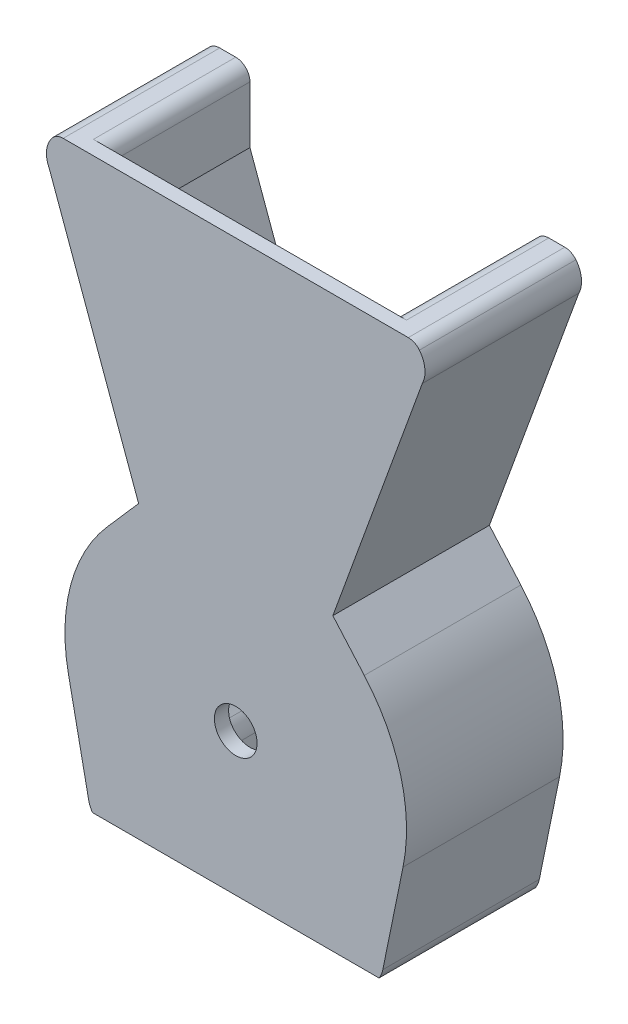
SolidWorks part; units mm, degrees
ref_plane "Front Plane" through (0, 0, 0) normal (0, 0, 1) x (1, 0, 0)
ref_plane "Top Plane" through (0, 0, 0) normal (0, 1, 0) x (1, 0, 0)
ref_plane "Right Plane" through (0, 0, 0) normal (1, 0, 0) x (0, 0, -1)
sketch "Boundaries" plane through (0, 0, 0) normal (0, 0, 1) x (1, 0, 0)
  line L1 (-80, 100) -> (80, 100) construction
  line L2 (-80, 100) -> (-80, -100) construction
  line L3 (-80, -100) -> (80, -100) construction
  line L4 (80, 100) -> (80, -100) construction
  point P0 (0, 0)
  point P7 (0, 100)
  point P8 (80, 0)
  dimension "D1" = 160
  dimension "D2" = 200
sketch "Sketch2" plane through (0, 0, 0) normal (0, 0, 1) x (1, 0, 0)
  line L0 (-80, -100) -> (80, -100) construction
  line L1 (-53.1957, 0) -> (53.1957, 0) construction
  line L4 (-50, 75) -> (50, 75) construction
  line L5 (-50, 75) -> (-22.7022, 0)
  line L6 (50, 75) -> (22.7022, 0)
  line L7 (-53.1957, 0) -> (-22.7022, 0) construction
  line L8 (-80, 100) -> (-50, 100)
  line L9 (-80, 100) -> (-80, -100)
  line L10 (-80, -100) -> (-35.3553, -100)
  line L11 (80, 100) -> (80, -100)
  line L12 (22.7022, 0) -> (53.1957, 0) construction
  line L13 (-50, 75) -> (-50, 100)
  line L14 (50, 75) -> (50, 100)
  line L15 (50, 100) -> (80, 100)
  line L16 (-37.6439, -17.092) -> (-22.7022, 0)
  line L17 (22.7022, 0) -> (37.6439, -17.092)
  line L20 (35.3553, -100) -> (80, -100)
  line L21 (-35.3553, -100) -> (35.3553, -100) construction
  line L22 (-35.3553, -14.6447) -> (35.3553, -85.3553) construction
  line L23 (-35.3553, -85.3553) -> (35.3553, -14.6447) construction
  line L24 (0, 0) -> (0, -50) construction
  line L26 (-35.3553, -100) -> (-35.3553, -85.3553)
  line L27 (35.3553, -100) -> (35.3553, -85.3553)
  arc A0 (-37.6439, -17.092) -> (-35.3553, -85.3553) centre (0, -50) ccw construction
  arc A1 (-37.6439, -17.092) -> (-35.3553, -85.3553) centre (0, -50) ccw
  arc A2 (35.3553, -85.3553) -> (37.6439, -17.092) centre (0, -50) ccw construction
  arc A3 (35.3553, -85.3553) -> (37.6439, -17.092) centre (0, -50) ccw
  circle A4 centre (0, -50) radius 50 construction
  point P12 (0, 0)
  point P13 (0, 75)
  point P26 (0, -100)
  point P31 (0, -50)
  point P34 (0, -50)
  dimension "D1" = 100
  dimension "D2" = 45
  dimension "D3" = 45
  dimension "D4" = 70
  dimension "D5" = 70
  dimension "D8" = 100
  dimension "D9" = 75
  dimension "D10" = 45.4045
extrude "Boss-Extrude1" add sketch "Sketch2" against normal blind 50
sketch "Sketch3" plane through (0, 0, 0) normal (0, 0, 1) x (1, 0, 0)
  line L0 (-29.9816, 20) -> (29.9816, 20)
  line L1 (-50, 75) -> (-22.7022, 0) construction
  line L2 (50, 75) -> (22.7022, 0) construction
  line L3 (29.9816, 20) -> (22.7022, 0)
  line L4 (22.7022, 0) -> (-22.7022, 0)
  line L5 (-22.7022, 0) -> (-29.9816, 20)
  dimension "D1" = 20
extrude "Boss-Extrude2" add sketch "Sketch3" against normal blind 10
chamfer "Chamfer1" distance 20 distance2 15 1 edges at (0, 20, -10) first distance on face at (0, 10, -10)
sketch "Sketch4" plane through (0, 0, 0) normal (0, 0, 1) x (1, 0, 0)
  line L1 (-80, 100) -> (80, 100)
  line L2 (-80, 100) -> (-80, -100)
  line L3 (-80, -100) -> (80, -100)
  line L4 (80, 100) -> (80, -100)
extrude "Boss-Extrude3" add sketch "Sketch4" along normal blind 5
fillet "Fillet1" radius 10 5 edges at (-35.3553, -85.3553, -25) (-22.7022, 0, -30) (22.7022, 0, -30) (0, 13.3333, 0) (35.3553, -85.3553, -25)
sketch "Sketch5" plane through (0, 0, 0) normal (0, 0, -1) x (-1, 0, 0)
  circle A0 centre (0, -50) radius 7.5
  dimension "D1" = 15
extrude "Cut-Extrude1" cut sketch "Sketch5" against normal up to surface (5 mm away) up to face at (0, 0, 5)
sketch "Sketch11" plane through (0, 0, -50) normal (0, 0, -1) x (-1, 0, 0)
  line L0 (80, -100) -> (-80, -100) construction
  line L1 (-35.3553, -100) -> (-35.3553, -85.3553) construction
  line L2 (-58.7842, -62.0174) -> (-51.673, -96.8026)
  line L3 (-80, -100) -> (-50.3387, -100)
  line L4 (0, -100) -> (0, 100) construction
  line L5 (34.1202, 2.1327) -> (45.1727, -10.5104)
  line L6 (60, 73.2367) -> (34.1202, 2.1327)
  line L7 (60, 73.2367) -> (65.537, 88.4494)
  line L8 (80, 100) -> (-80, 100) construction
  line L9 (-50, 75) -> (-50, 100) construction
  line L10 (-60, 73.2367) -> (-65.537, 88.4494)
  line L11 (-80, 100) -> (-80, -100) construction
  line L12 (-45.3553, -89.2797) -> (-45.3553, -100)
  line L13 (-34.1202, 2.1327) -> (-45.1727, -10.5104)
  line L14 (-60, 73.2367) -> (-34.1202, 2.1327)
  line L15 (-60, 100) -> (-60, 73.2367)
  line L17 (-34.1202, 2.1327) -> (-45.1727, -10.5104)
  line L18 (-60, 73.2367) -> (-34.1202, 2.1327)
  line L19 (-80, 100) -> (-80, -100)
  line L20 (-62.4749, 100) -> (-80, 100)
  line L21 (62.4749, 100) -> (80, 100)
  line L22 (80, 100) -> (80, -100)
  line L23 (80, -100) -> (50.3387, -100)
  line L24 (58.7842, -62.0174) -> (51.673, -96.8026)
  circle A0 centre (-42.8553, -95) radius 1.5 construction
  arc A1 (-51.673, -96.8026) -> (-50.3387, -100) centre (-42.8553, -95) ccw
  arc A2 (62.4749, 100) -> (65.537, 88.4494) centre (57.5, 92.5) cw
  arc A3 (51.673, -96.8026) -> (50.3387, -100) centre (42.8553, -95) cw
  arc A4 (45.1727, -10.5104) -> (58.7842, -62.0174) centre (0, -50) cw
  circle A6 centre (-57.5, 92.5) radius 1.5 construction
  arc A7 (-62.4749, 100) -> (-65.537, 88.4494) centre (-57.5, 92.5) ccw
  arc A9 (-45.1727, -10.5104) -> (-45.3553, -89.2797) centre (0, -50) ccw
  arc A10 (-45.1727, -10.5104) -> (-58.7842, -62.0174) centre (0, -50) ccw
  dimension "D3" = 3
  dimension "D4" = 7.5
  dimension "D5" = 7.5
  dimension "D7" = 7.5
  dimension "D8" = 7.5
  dimension "D2" = 7.5
  dimension "D6" = 5
  dimension "D1" = 10
extrude "Cut-Extrude5" cut sketch "Sketch11" against normal through all and the other way through all
fillet "Fillet4" radius 5 6 edges at (-50, 100, -25) (50, 100, -25) (-35.3553, -100, -25) (35.3553, -100, -25) (-62.4749, 100, -22.5) (62.4749, 100, -22.5)
ref_plane "MidPlane" through (0, 0, -25) normal (0, 0, -1) x (-1, 0, 0)
ref_axis "Food Drop Axis" through (0, 124.9402, -25) along (0, -1, 0)
sketch "Sketch12" plane through (0, 0, -50) normal (0, 0, -1) x (-1, 0, 0)
  circle A0 centre (-57.5, 92.5) radius 2
  circle A1 centre (57.5, 92.5) radius 2
  circle A2 centre (-42.8553, -95) radius 2
  circle A3 centre (42.8553, -95) radius 2
  dimension "D1" = 4
extrude "Cut-Extrude6" cut sketch "Sketch12" against normal blind 10
sketch "Sketch13" plane through (0, 0, -50) normal (0, 0, -1) x (-1, 0, 0)
  line L0 (-35.3553, -89.2797) -> (-35.3553, -95) construction
  line L1 (-45.3553, -87.6922) -> (-22.8553, -87.6922) construction
  line L2 (-45.3553, -87.6922) -> (-45.3553, -89.2797) construction
  line L3 (-45.3553, -89.2797) -> (-22.8553, -89.2797) construction
  line L4 (-22.8553, -87.6922) -> (-22.8553, -89.2797) construction
  line L5 (-45.5553, -87.4922) -> (-22.6553, -87.4922)
  line L6 (-22.6553, -87.4922) -> (-22.6553, -89.4797)
  line L7 (-45.5553, -89.4797) -> (-22.6553, -89.4797)
  line L8 (-45.5553, -87.4922) -> (-45.5553, -89.4797)
  line L9 (0, -100) -> (0, -49.363) construction
  line L10 (40.3553, -100) -> (-40.3553, -100) construction
  line L11 (45.5553, -87.4922) -> (45.5553, -89.4797)
  line L12 (45.5553, -89.4797) -> (22.6553, -89.4797)
  line L13 (22.6553, -87.4922) -> (22.6553, -89.4797)
  line L14 (45.5553, -87.4922) -> (22.6553, -87.4922)
  dimension "D1" = 1.5875
  dimension "D2" = 10
  dimension "D3" = 12.5
  dimension "D4" = 0.2
extrude "Cut-Extrude7" [suppressed] cut sketch "Sketch13" against normal up to surface (50 mm away)
fillet "Fillet5" [suppressed] radius 1
